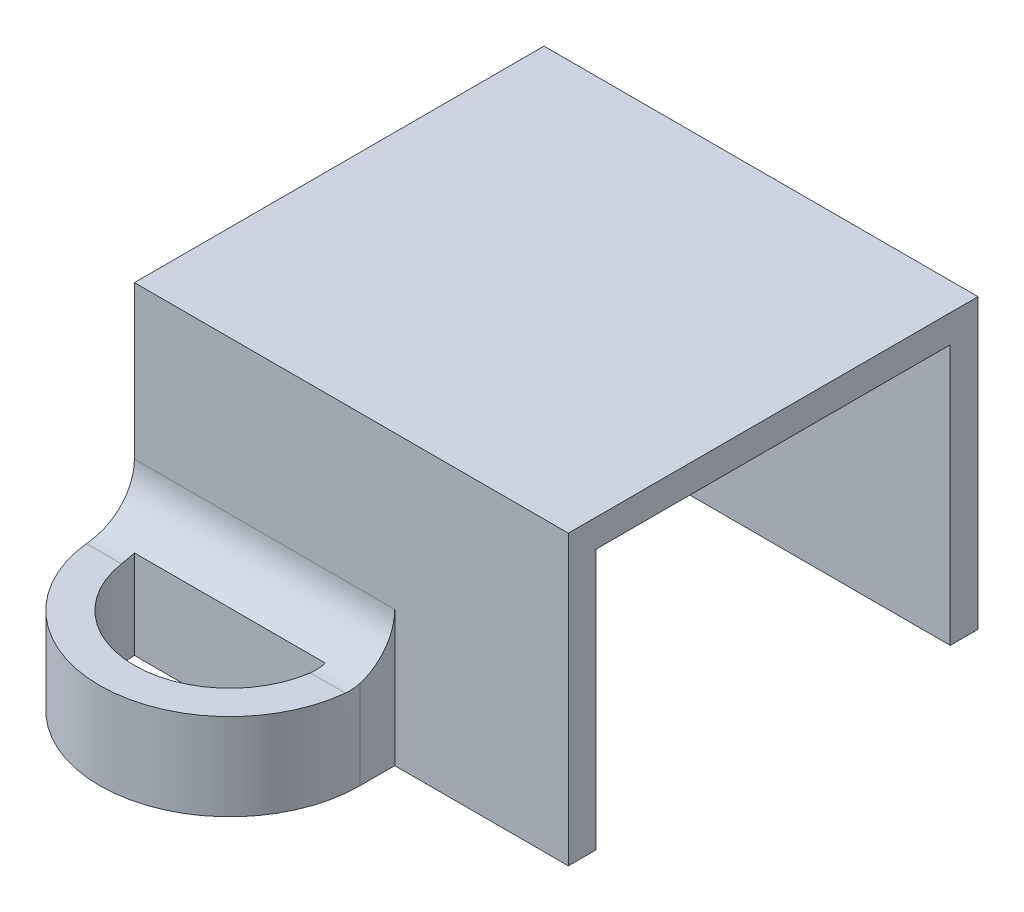
SolidWorks part; units mm, degrees
ref_plane "Front Plane" through (0, 0, 0) normal (0, 0, 1) x (1, 0, 0)
ref_plane "Top Plane" through (0, 0, 0) normal (0, 1, 0) x (1, 0, 0)
ref_plane "Right Plane" through (0, 0, 0) normal (1, 0, 0) x (0, 0, -1)
sketch "Sketch1" plane through (0, 0, 0) normal (1, 0, 0) x (0, 0, -1)
  line L0 (0, 0) -> (-1.016, 0)
  line L2 (0, 0) -> (0, 9.525)
  line L3 (0, 9.525) -> (12.954, 9.525)
  line L4 (12.954, 0) -> (12.954, 9.525)
  line L5 (13.97, 0) -> (12.954, 0)
  line L6 (13.97, 0) -> (13.97, 10.541)
  line L7 (13.97, 10.541) -> (-1.016, 10.541)
  line L8 (-1.016, 0) -> (-1.016, 10.541)
  dimension "D1" = 12.954
  dimension "D2" = 9.525
  dimension "D3" = 10.541
  dimension "D4" = 1.016
  dimension "D5" = 1.016
extrude "Boss-Extrude1" add sketch "Sketch1" along normal blind 15.875
sketch "Sketch2" plane through (0, 0, 0) normal (0, -1, 0) x (1, 0, 0)
  line L0 (0, 1.016) -> (9.525, 1.016) construction
  line L1 (15.875, 1.016) -> (0, 1.016) construction
  line L2 (4.7625, 1.016) -> (4.7625, 2.286) construction
  line L3 (9.525, 2.286) -> (9.525, 1.016)
  line L4 (9.525, 1.016) -> (0, 1.016)
  line L5 (0, 1.016) -> (0, 2.286)
  line L6 (0, 1.016) -> (0, 0) construction
  arc A0 (9.525, 2.286) -> (0, 2.286) centre (4.7625, 2.286) ccw
  dimension "D2" = 9.525
  dimension "D1" = 9.525
  dimension "D3" = 1.27
extrude "Boss-Extrude2" add sketch "Sketch2" against normal blind 3.175
sketch "Sketch4" plane through (0, 3.175, 0) normal (0, 1, 0) x (1, 0, 0)
  line L8 (8.255, -2.286) -> (1.27, -2.286)
  line L11 (8.255, -2.286) -> (1.27, -2.286)
  arc A2 (1.27, -2.286) -> (8.255, -2.286) centre (4.7625, -2.286) ccw
  arc A3 (1.27, -2.286) -> (8.255, -2.286) centre (4.7625, -2.286) ccw
  dimension "D1" = 1.27
extrude "Cut-Extrude1" cut sketch "Sketch4" against normal up to next
fillet "Fillet2" radius 1.778 1 edges at (4.7625, 3.175, 1.016)
ref_plane "Plane1" through (0, 0, -6.477) normal (0, 0, 1) x (1, 0, 0)
mirror "Mirror2" about plane through (0, 0, -6.477) normal (0, 0, 1) of "Boss-Extrude2"
mirror "Mirror3" about plane through (0, 0, -6.477) normal (0, 0, 1) of "Cut-Extrude1"
fillet "Fillet3" radius 1.778 1 edges at (4.7625, 3.175, -13.97)
